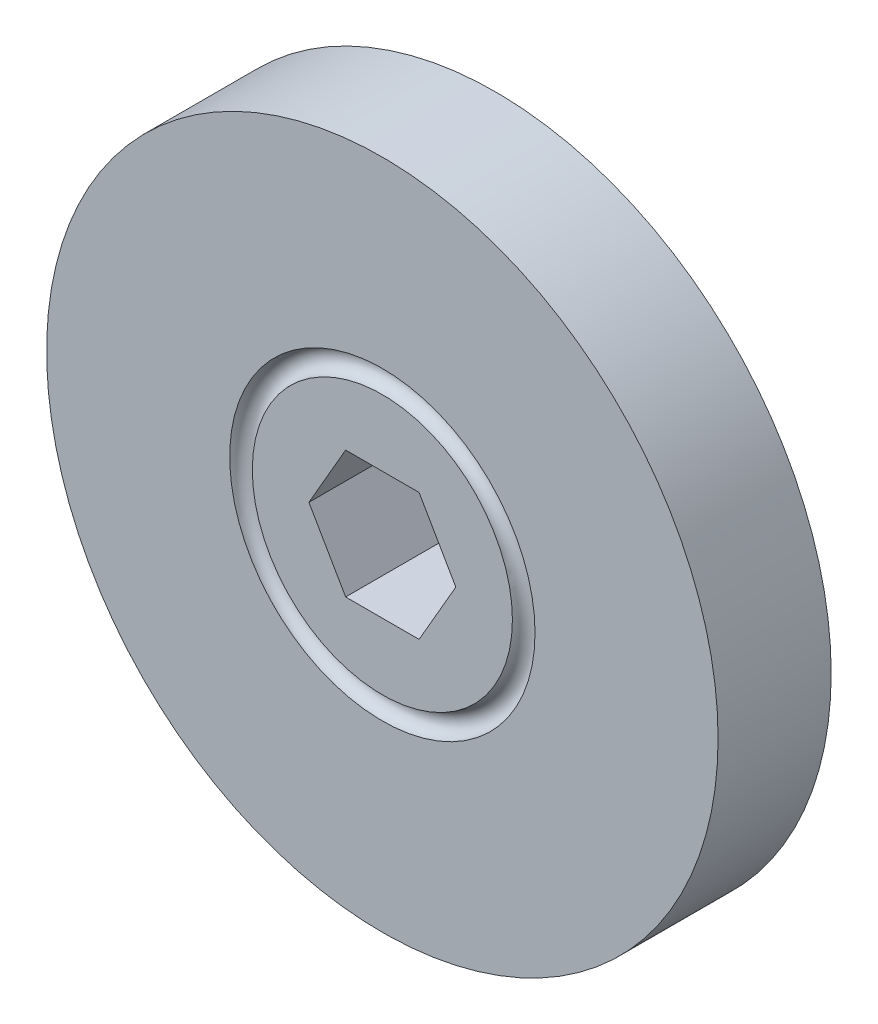
SolidWorks part; units mm, degrees
ref_plane "Front Plane" through (0, 0, 0) normal (0, 0, 1) x (1, 0, 0)
ref_plane "Top Plane" through (0, 0, 0) normal (0, 1, 0) x (1, 0, 0)
ref_plane "Right Plane" through (0, 0, 0) normal (1, 0, 0) x (0, 0, -1)
sketch "Sketch1" plane through (0, 0, 0) normal (1, 0, 0) x (0, 0, -1)
  line L0 (0, 0) -> (0, 30.1625) construction
  line L1 (-5.08, 30.1625) -> (5.08, 30.1625)
  line L2 (5.08, 30.1625) -> (5.08, 13.716)
  line L3 (5.08, 11.684) -> (5.08, 0)
  line L4 (-5.08, 11.684) -> (-5.08, 0)
  line L5 (-5.08, 30.1625) -> (-5.08, 13.716)
  line L6 (-5.08, 0) -> (5.08, 0)
  arc A0 (5.08, 13.716) -> (5.08, 11.684) centre (5.08, 12.7) ccw
  arc A1 (-5.08, 13.716) -> (-5.08, 11.684) centre (-5.08, 12.7) cw
  point P6 (0, 30.1625)
  dimension "D1" = 10.16
  dimension "D4" = 1.016
  dimension "D2" = 30.1625
  dimension "D3" = 12.7
revolve "Revolve1" add sketch "Sketch1" angle 360 about L6
sketch "Sketch2" plane through (0, 0, 5.08) normal (0, 0, 1) x (1, 0, 0)
  line L1 (-3.2996, 5.715) -> (-6.5991, 0)
  line L2 (-6.5991, 0) -> (-3.2996, -5.715)
  line L3 (-3.2996, -5.715) -> (3.2996, -5.715)
  line L4 (3.2996, -5.715) -> (6.5991, 0)
  line L5 (6.5991, 0) -> (3.2996, 5.715)
  line L6 (3.2996, 5.715) -> (-3.2996, 5.715)
  circle A0 centre (0, 0) radius 5.715 construction
  dimension "D1" = 11.43
extrude "Cut-Extrude1" cut sketch "Sketch2" against normal up to next
